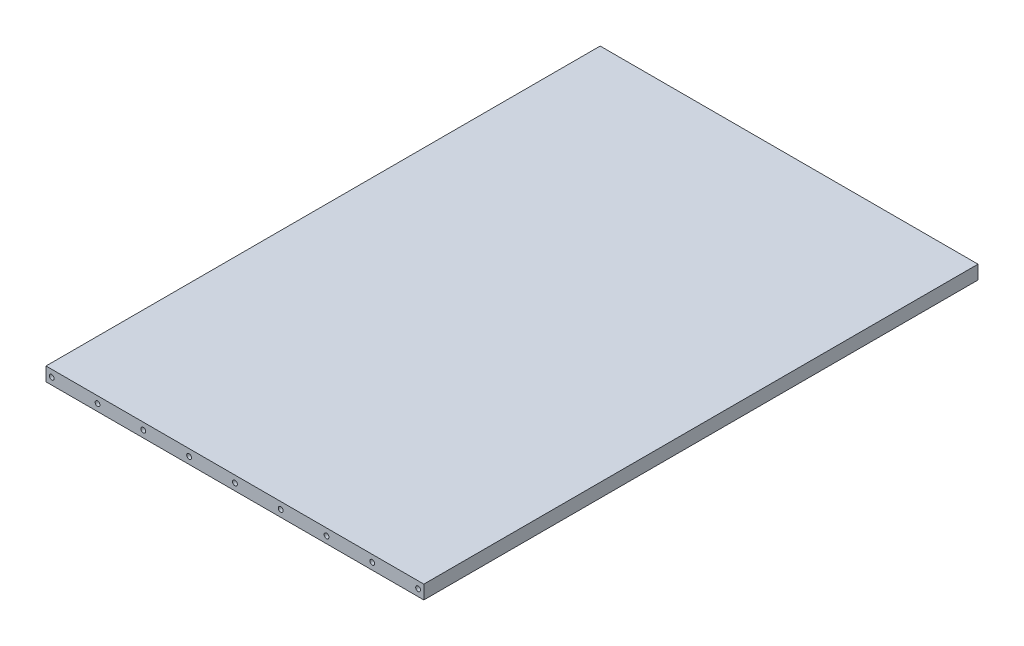
SolidWorks part; units mm, degrees
ref_plane "Front Plane" through (0, 0, 0) normal (0, 0, 1) x (1, 0, 0)
ref_plane "Top Plane" through (0, 0, 0) normal (0, 1, 0) x (1, 0, 0)
ref_plane "Right Plane" through (0, 0, 0) normal (1, 0, 0) x (0, 0, -1)
sketch "Sketch1" plane through (0, 0, 0) normal (0, 0, 1) x (1, 0, 0)
  line L1 (-165, 6) -> (165, 6)
  line L2 (-165, 6) -> (-165, -6)
  line L3 (-165, -6) -> (165, -6)
  line L4 (165, 6) -> (165, -6)
  line L5 (-165, 6) -> (165, -6) construction
  line L6 (-165, -6) -> (165, 6) construction
  point P0 (0, 0)
  circle B0 centre (0, 0) radius 2.1
  circle B1 centre (40, 0) radius 2.1
  circle B2 centre (80, 0) radius 2.1
  circle B3 centre (120, 0) radius 2.1
  circle B4 centre (160, 0) radius 2.1
  circle B5 centre (-40, 0) radius 2.1
  circle B6 centre (-80, 0) radius 2.1
  circle B7 centre (-120, 0) radius 2.1
  circle B8 centre (-160, 0) radius 2.1
  dimension "D1" = 12
  dimension "D2" = 330
sketch_block_instance "Block1-1"
sketch_block "Block1"
extrude "Boss-Extrude1" add sketch "Sketch1" along normal blind 484
